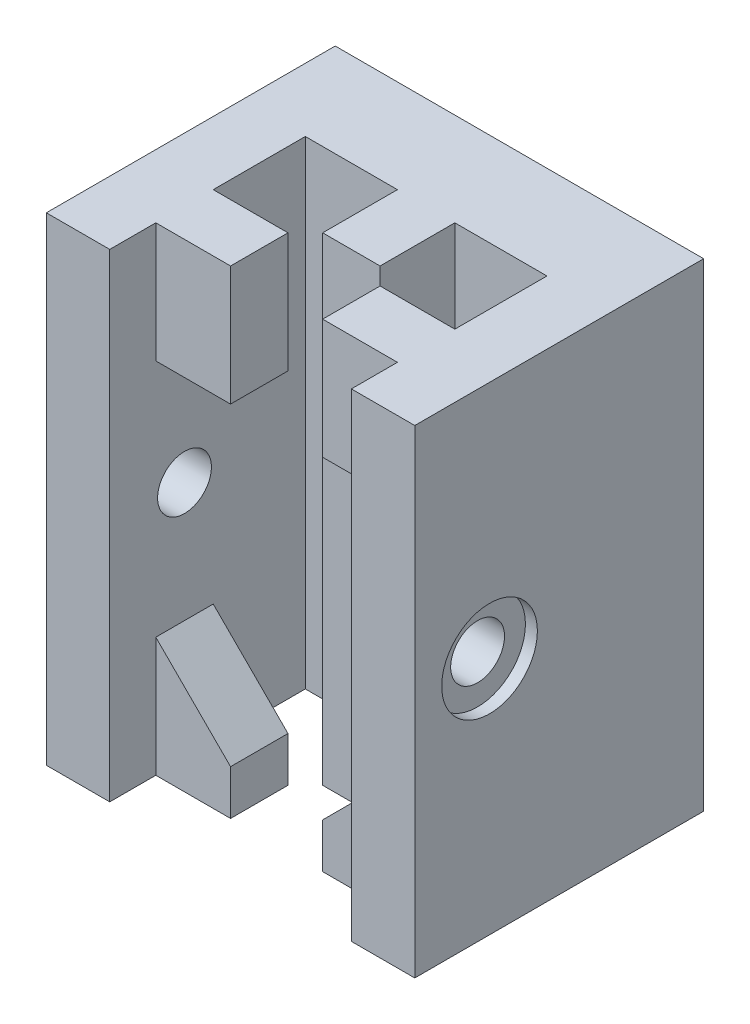
SolidWorks part; units mm, degrees
ref_plane "Plan de face" through (0, 0, 0) normal (0, 0, 1) x (1, 0, 0)
ref_plane "Plan de dessus" through (0, 0, 0) normal (0, 1, 0) x (1, 0, 0)
ref_plane "Plan de droite" through (0, 0, 0) normal (1, 0, 0) x (0, 0, -1)
sketch "Base" plane through (0, 0, 0) normal (0, 1, 0) x (1, 0, 0)
  line L0 (-3.85, -2.4) -> (-3.85, 2.4)
  line L1 (-3.85, 2.4) -> (-10.1, 2.4)
  line L2 (-10.1, 2.4) -> (-10.1, 10.1)
  line L3 (-10.1, 10.1) -> (-2.4, 10.1)
  line L4 (-2.4, 10.1) -> (-2.4, 3.85)
  line L5 (-2.4, 3.85) -> (2.4, 3.85)
  line L6 (0, -55) -> (0, 55) construction
  line L7 (2.4, 10.1) -> (2.4, 3.85)
  line L8 (10.1, 10.1) -> (2.4, 10.1)
  line L9 (10.1, 2.4) -> (10.1, 10.1)
  line L10 (3.85, 2.4) -> (10.1, 2.4)
  line L11 (3.85, -2.4) -> (3.85, 2.4)
  line L12 (-55, 0) -> (55, 0) construction
  line L13 (3.85, -2.4) -> (10.1, -2.4)
  line L14 (10.1, -2.4) -> (10.1, -6.25)
  line L20 (-10.1, -2.4) -> (-10.1, -6.25)
  line L21 (-3.85, -2.4) -> (-10.1, -2.4)
  line L23 (-15.4, 15.4) -> (15.4, 15.4)
  line L24 (-15.4, 15.4) -> (-15.4, -6.25)
  line L26 (15.4, 15.4) -> (15.4, -6.25)
  line L27 (-15.4, 15.4) -> (0, 0) construction
  line L28 (0, 0) -> (15.4, 15.4) construction
  line L29 (-10.1, -6.25) -> (-15.4, -6.25)
  line L30 (10.1, -6.25) -> (15.4, -6.25)
  line L31 (10.1, -10.1) -> (15.4, -15.4) construction
  point P2 (-3.85, 0)
  point P3 (0, 3.85)
  point P27 (0, 0)
  dimension "D1" = 4.8
  dimension "D2" = 4.8
  dimension "D3" = 6.25
  dimension "D4" = 7.7
  dimension "D5" = 30.8
extrude "Boss.-Extru.1" add sketch "Base" along normal mid plane 40
hole_wizard "Chambrage pour vis à six pans creux M41" positions "Esquisse4" profile "Esquisse5" counterbore size "M4" standard "ISO" end condition up to next
sketch "Esquisse4" plane through (15.4, 0, 0) normal (1, 0, 0) x (0, 0, -1)
  point P0 (0, 0)
sketch "Esquisse5" plane through (15.4, 0, 0) normal (0, 1, 0) x (0, 0, -1)
  line L0 (0, 0) -> (0, 11.55)
  line L1 (0, 11.55) -> (2.25, 11.55)
  line L3 (2.25, 11.55) -> (2.25, 1)
  line L4 (2.25, 1) -> (4, 1)
  line L5 (4, 1) -> (4, 0)
  line L7 (4, 0) -> (0, 0)
  line L11 (0, -6.35) -> (0, 107.95) construction
  dimension "Diamètre du perçage jusqu'au prochain" = 4.5
  dimension "Profondeur du perçage jusqu'au prochain" = 11.55
  dimension "Diamètre du chambrage" = 8
  dimension "Profondeur du chambrage" = 1
mirror "Symétrie1" about plane through (0, 0, 0) normal (1, 0, 0) of "Chambrage pour vis à six pans creux M41"
sketch "Esquisse6" plane through (0, 0, 0) normal (0, 0, 1) x (1, 0, 0)
  line L0 (10.1, 20) -> (10.1, -20) construction
  line L1 (-10.1, 10) -> (10.1, 10)
  line L2 (-10.1, 10) -> (-10.1, -10)
  line L3 (-10.1, -10) -> (10.1, -10)
  line L4 (10.1, 10) -> (10.1, -10)
  line L5 (-10.1, 10) -> (10.1, -10) construction
  line L6 (-10.1, -10) -> (10.1, 10) construction
  point P0 (0, 0)
  dimension "D1" = 20
extrude "Enlèv. mat.-Extru.1" cut sketch "Esquisse6" against normal mid plane 6
sketch "Esquisse14" plane through (0, -20, 0) normal (0, -1, 0) x (1, 0, 0)
  line L0 (15.4, 6.25) -> (15.4, -15.4) construction
  line L1 (-15.4, -15.4) -> (15.4, -15.4)
  line L2 (-15.4, -15.4) -> (-15.4, -17.9)
  line L3 (-15.4, -17.9) -> (15.4, -17.9)
  line L4 (15.4, -15.4) -> (15.4, -17.9)
  dimension "D1" = 2.5
extrude "Boss.-Extru.3" add sketch "Esquisse14" against normal up to vertex (40 mm away) up to point (-15.4, 20, -15.4)
chamfer "Chanfrein1" distance 6.25 angle 45 2 edges at (3.85, -10, 0) (-3.85, -10, 0)
